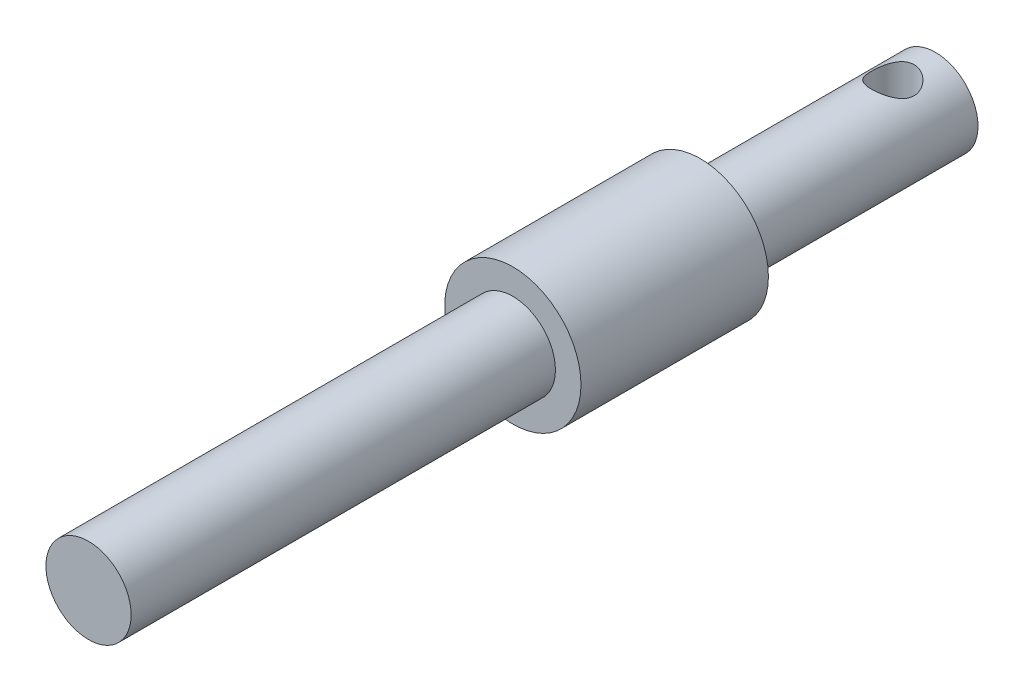
SolidWorks part; units mm, degrees
material "Plain Carbon Steel"
ref_plane "Front Plane" through (0, 0, 0) normal (0, 0, 1) x (1, 0, 0)
ref_plane "Top Plane" through (0, 0, 0) normal (0, 1, 0) x (1, 0, 0)
ref_plane "Right Plane" through (0, 0, 0) normal (1, 0, 0) x (0, 0, -1)
sketch "Sketch1" plane through (0, 0, 0) normal (0, 0, 1) x (1, 0, 0)
  line L2 (0, 0) -> (0, -4.6729) construction
  circle A0 centre (0, 0) radius 2.5
  circle A1 centre (0, 0) radius 4
  dimension "D1" = 5
  dimension "D3" = 8
extrude "Boss-Extrude1" add sketch "Sketch1" along normal blind 13.8 contours A0
extrude "Boss-Extrude3" add sketch "Sketch1<4>" along normal blind 11 from surface contours A1 starting at face at (2.5, 0, 13.8)
sketch "Sketch1<4>" plane through (0, 0, 0) normal (0, 0, 1) x (1, 0, 0) same geometry as "Sketch1"
extrude "Boss-Extrude2" add sketch "Sketch1<3>" along normal blind 24.9 from surface contours L2 A0 | A0 L2 region at (-1.7178, 1.7178, 0) starting at face at (4, 0, 24.8)
sketch "Sketch1<3>" plane through (0, 0, 0) normal (0, 0, 1) x (1, 0, 0) same geometry as "Sketch1"
cosmetic thread "Cosmetic Thread1" parameters "D2"=4.11
sketch "Sketch17" plane through (0, 0, 0) normal (0, 1, 0) x (1, 0, 0)
  line L0 (2.5, 0) -> (-2.5, 0) construction
  circle A0 centre (0, -2.5) radius 1.25
  dimension "D2" = 2.5
  dimension "D1" = 2.5
extrude "Cut-Extrude1" cut sketch "Sketch17" against normal through all both and the other way through all
